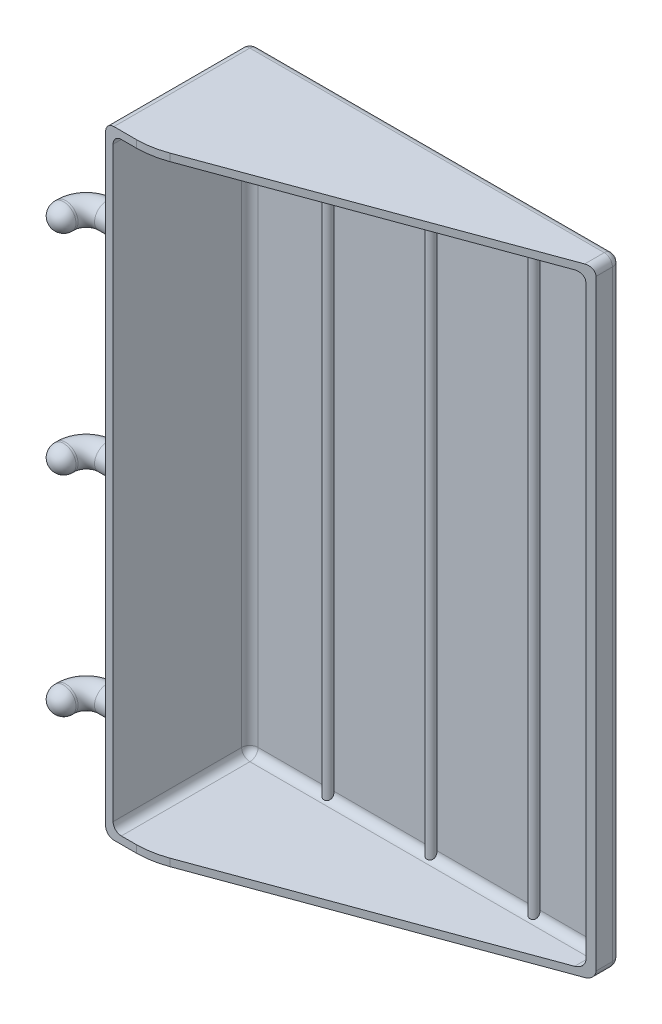
SolidWorks part; units mm, degrees
note: '?' marks a value the reader was unsure of.
ref_plane "Front Plane" through (0, 0, 0) normal (1, 0, 0) x (0, 1, 0)
ref_plane "Top Plane" through (0, 0, 0) normal (0, 0, 1) x (0, 1, 0)
ref_plane "Right Plane" through (0, 0, 0) normal (0, 1, 0) x (-1, 0, 0)
ref_axis "x axis" through (-88.99, 0, 0) along (1, 0, 0)?
ref_axis "y xxis" through (0, 88.99, 0) along (0, -1, 0)?
ref_axis "z axis" through (0, 0, 55) along (0, 0, -1)?
sketch "Sketch1" plane through (0, 0, 0) normal (0, 0, 1) x (0, 1, 0)
  line L1 (-75, -45) -> (75, -45)
  line L2 (-75, -45) -> (-75, 45)
  line L3 (-75, 45) -> (75, 45)
  line L4 (75, -45) -> (75, 45)
  line L5 (-75, -45) -> (75, 45) construction
  line L6 (-75, 45) -> (75, -45) construction
  point P0 (0, 0)
  dimension "D1" = 90
  dimension "D2" = 150
extrude "Boss-Extrude1" add sketch "Sketch1" along normal blind 1.8
sketch "Sketch2" plane through (0, 0, 1.8) normal (0, 0, 1) x (1, 0, 0)
  line L4 (43.2, 73.2) -> (-43.2, 73.2)
  line L5 (-43.2, 73.2) -> (-43.2, -73.2)
  line L6 (-43.2, -73.2) -> (43.2, -73.2)
  line L7 (43.2, -73.2) -> (43.2, 73.2)
  line L8 (45, 75) -> (-45, 75)
  line L9 (-45, 75) -> (-45, -75)
  line L10 (-45, -75) -> (45, -75)
  line L11 (45, -75) -> (45, 75)
  line L12 (45, 75) -> (-45, 75)
  line L13 (-45, 75) -> (-45, -75)
  line L14 (-45, -75) -> (45, -75)
  line L15 (45, -75) -> (45, 75)
  dimension "D1" = 0
  dimension "D2" = 1.8
extrude "Boss-Extrude3" add sketch "Sketch2" along normal offset from surface (33.2 mm away) 35 up to face at (0, 0, 0)
sketch "Sketch3" plane through (0, -75, 0) normal (0, -1, 0) x (1, 0, 0)
  line L0 (-34, 35) -> (45, 6)
  line L1 (45, 35) -> (-45, 35) construction
  line L2 (45, 35) -> (45, 0) construction
  line L3 (45, 6) -> (45, 35)
  line L4 (45, 35) -> (-34, 35)
  line L5 (-45, 35) -> (-45, 0) construction
  dimension "D1" = 11
  dimension "D2" = 6
extrude "Cut-Extrude1" cut sketch "Sketch3" against normal up to surface (150 mm away) up to face at (0, 75, 17.5)
sketch "Sketch5" plane through (0, 0, 0) normal (0, 1, 0) x (-1, 0, 0)
  line L0 (45, 30.2) -> (49.5, 30.2)
  line L1 (45, 35) -> (45, 0) construction
  line L2 (54.5, 35.2) -> (54.5, 38.7)
  line L3 (45, 35) -> (45, 30.2) construction
  line L4 (45, 30.2) -> (45, 4.8) construction
  line L5 (45, 4.8) -> (45, 0) construction
  arc A0 (49.5, 30.2) -> (54.5, 35.2) centre (49.5, 35.2) ccw
  point P14 (54.0823, 38.3167)
  point P15 (51.1176, 41.2618)
  point P16 (53.9177, 38.9236)
  point P17 (54.2564, 38.8749)
  point P18 (51.9469, 39.9531)
  point P19 (52.9191, 39.8368)
  dimension "D1" = 5
  dimension "D2" = 25.4
  dimension "D3" = 9.5
  dimension "D4" = 8.5
  dimension "D5" = 4.8
sweep "Sweep2" add path "Sketch5" circular profile diameter 6 parameters "D3"=6
sketch "Sketch18" plane through (0, 0, 0) normal (0, 1, 0) x (-1, 0, 0)
  line L0 (45, 4.8) -> (55, 4.8)
  dimension "D1" = 10
sweep "Sweep3" add path "Sketch18" circular profile diameter 6 parameters "D3"=6
fillet "Fillet2" radius 3 2 edges at (-57.5, 0, 38.7) (-55, 0, 7.8)
pattern_linear "LPattern1" count 2 spacing 50.8 along (0, -1, 0) count 2 spacing 50.8 along (0, 1, 0) of "Sweep2", "Sweep3", "Fillet2"
fillet "Fillet3" radius 2 16 edges at (43.2, 0, 1.8) (-43.2, 73.2, 18.4) (0, 73.2, 1.8) (-43.2, 0, 1.8) (0, -73.2, 1.8) (-43.2, -73.2, 18.4) (-45, 75, 17.5) (-45, -75, 17.5) (0, -75, 0) (45, 0, 0) (-45, 0, 0) (0, 75, 0) (45, -75, 3) (43.2, -73.2, 4.2304) (43.2, 73.2, 4.2304) (45, 75, 3)
fillet "Fillet4" radius 20 2 edges at (-34, 74.1, 35) (-34, -74.1, 35)
sketch "Sketch66" plane through (0, 0, 0) normal (0, 1, 0) x (-1, 0, 0)
  line L0 (-26, 1.8) -> (0, 1.8) construction
  line L1 (-26, 1.8) -> (-26, 3) construction
  line L3 (41.2, 1.8) -> (-41.2, 1.8) construction
  line L4 (-27.25, 1.8) -> (-24.75, 1.8)
  line L5 (-26, 1.8) -> (-26, 1.749) construction
  line L6 (0, 1.8) -> (0, 0) construction
  line L7 (-2.25, 1.8) -> (0.25, 1.8)
  line L8 (22.75, 1.8) -> (25.25, 1.8)
  arc A0 (-27.25, 1.8) -> (-24.75, 1.8) centre (-26, 1.749) cw
  arc A1 (-2.25, 1.8) -> (0.25, 1.8) centre (-1, 1.749) cw
  arc A2 (22.75, 1.8) -> (25.25, 1.8) centre (24, 1.749) cw
  dimension "D2" = 2.5
  dimension "D4" = 3
  dimension "D5" = 26
  dimension "D1" = 1.2
extrude "Boss-Extrude4" add sketch "Sketch66" along normal up to surface and the other way up to surface
